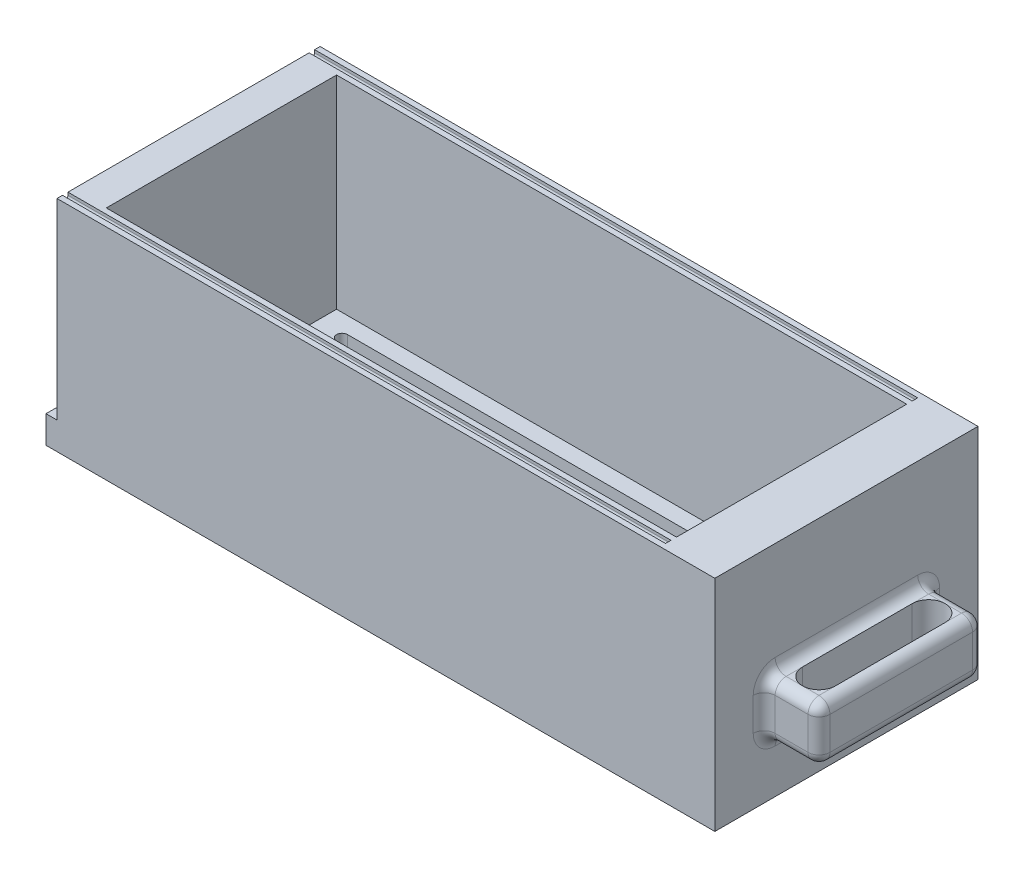
SolidWorks part; units mm, degrees
ref_plane "Front Plane" through (0, 0, 0) normal (0, 0, 1) x (1, 0, 0)
ref_plane "Top Plane" through (0, 0, 0) normal (0, 1, 0) x (1, 0, 0)
ref_plane "Right Plane" through (0, 0, 0) normal (1, 0, 0) x (0, 0, -1)
sketch "Sketch1" plane through (0, 0, 0) normal (0, 1, 0) x (1, 0, 0)
  line L1 (0, 0) -> (120, 0)
  line L2 (0, 0) -> (0, 48)
  line L3 (0, 48) -> (120, 48)
  line L4 (120, 0) -> (120, 48)
  dimension "D1" = 120
  dimension "D2" = 48
extrude "Boss-Extrude1" add sketch "Sketch1" along normal blind 40
sketch "Sketch2" plane through (0, 40, 0) normal (0, 1, 0) x (1, 0, 0)
  line L1 (6, 48) -> (74, 48)
  line L2 (6, 48) -> (6, 45)
  line L3 (6, 45) -> (74, 45)
  line L4 (74, 48) -> (74, 45)
  line L5 (120, 0) -> (120, 48) construction
  line L6 (0, 48) -> (120, 48) construction
  dimension "D1" = 3
  dimension "D2" = 46
  dimension "D3" = 68
extrude "Boss-Extrude2" [suppressed] add sketch "Sketch2" along normal blind 15
sketch "Sketch3" plane through (0, 40, 0) normal (0, 1, 0) x (1, 0, 0)
  line L1 (110, 45) -> (6, 45)
  line L2 (110, 45) -> (110, 3)
  line L3 (110, 3) -> (6, 3)
  line L4 (6, 45) -> (6, 3)
  line L5 (120, 0) -> (120, 48) construction
  line L6 (0, 0) -> (120, 0) construction
  line L7 (0, 48) -> (120, 48) construction
  dimension "D1" = 104
  dimension "D2" = 10
  dimension "D3" = 3
  dimension "D4" = 3
extrude "Cut-Extrude1" cut sketch "Sketch3" against normal blind 37
sketch "Sketch5" plane through (0, 3, 0) normal (0, 1, 0) x (1, 0, 0)
  line L0 (11, 41) -> (105, 41) construction
  line L1 (11, 42) -> (105, 42)
  line L2 (11, 40) -> (105, 40)
  line L3 (6, 45) -> (6, 3) construction
  line L4 (110, 3) -> (110, 45) construction
  line L5 (110, 45) -> (6, 45) construction
  line L8 (11, 35.1) -> (105, 35.1)
  line L11 (11, 37.1) -> (105, 37.1)
  line L14 (11, 36.1) -> (105, 36.1) construction
  line L17 (11, 30.2) -> (105, 30.2)
  line L20 (11, 32.2) -> (105, 32.2)
  line L23 (11, 31.2) -> (105, 31.2) construction
  line L26 (11, 25.3) -> (105, 25.3)
  line L28 (11, 27.3) -> (105, 27.3)
  line L29 (11, 26.3) -> (105, 26.3) construction
  line L30 (11, 20.4) -> (105, 20.4)
  line L31 (11, 22.4) -> (105, 22.4)
  line L32 (11, 21.4) -> (105, 21.4) construction
  line L33 (11, 15.5) -> (105, 15.5)
  line L34 (11, 17.5) -> (105, 17.5)
  line L35 (11, 16.5) -> (105, 16.5) construction
  line L36 (11, 10.6) -> (105, 10.6)
  line L37 (11, 12.6) -> (105, 12.6)
  line L38 (11, 11.6) -> (105, 11.6) construction
  line L39 (11, 5.7) -> (105, 5.7)
  line L40 (11, 7.7) -> (105, 7.7)
  line L41 (11, 6.7) -> (105, 6.7) construction
  arc A0 (11, 42) -> (11, 40) centre (11, 41) ccw
  arc A1 (105, 40) -> (105, 42) centre (105, 41) ccw
  arc A16 (11, 37.1) -> (11, 35.1) centre (11, 36.1) ccw
  arc A17 (105, 35.1) -> (105, 37.1) centre (105, 36.1) ccw
  arc A18 (11, 32.2) -> (11, 30.2) centre (11, 31.2) ccw
  arc A19 (105, 30.2) -> (105, 32.2) centre (105, 31.2) ccw
  arc A20 (11, 27.3) -> (11, 25.3) centre (11, 26.3) ccw
  arc A21 (105, 25.3) -> (105, 27.3) centre (105, 26.3) ccw
  arc A22 (11, 22.4) -> (11, 20.4) centre (11, 21.4) ccw
  arc A23 (105, 20.4) -> (105, 22.4) centre (105, 21.4) ccw
  arc A24 (11, 17.5) -> (11, 15.5) centre (11, 16.5) ccw
  arc A25 (105, 15.5) -> (105, 17.5) centre (105, 16.5) ccw
  arc A26 (11, 12.6) -> (11, 10.6) centre (11, 11.6) ccw
  arc A27 (105, 10.6) -> (105, 12.6) centre (105, 11.6) ccw
  arc A28 (11, 7.7) -> (11, 5.7) centre (11, 6.7) ccw
  arc A29 (105, 5.7) -> (105, 7.7) centre (105, 6.7) ccw
  point P2 (58, 41)
  point P17 (58, 36.1)
  point P24 (58, 31.2)
  point P31 (58, 26.3)
  point P38 (58, 21.4)
  point P45 (58, 16.5)
  point P52 (58, 11.6)
  point P59 (58, 6.7)
  dimension "D1" = 1
  dimension "D2" = 5
  dimension "D3" = 5
  dimension "D4" = 3
  dimension "D5" = 8
extrude "Cut-Extrude2" cut sketch "Sketch5" against normal blind 37
sketch "Sketch7" plane through (0, 0, 0) normal (-1, 0, 0) x (0, 0, 1)
  line L0 (-1.5, 39.5) -> (-1.5, 40.5) construction
  line L2 (-2, 39.5) -> (-2, 40.5)
  line L3 (-1, 39.5) -> (-1, 40.5)
  line L6 (-48, 40) -> (0, 40) construction
  line L7 (0, 40) -> (0, 0) construction
  arc A0 (-2, 39.5) -> (-1, 39.5) centre (-1.5, 39.5) ccw
  arc A1 (-1, 40.5) -> (-2, 40.5) centre (-1.5, 40.5) ccw
  point P4 (-1.5, 40)
  dimension "D2" = 0.5
  dimension "D1" = 1.5
  dimension "D3" = 1
extrude "Cut-Extrude4" cut sketch "Sketch7" against normal blind 110
ref_plane "Plane1" through (0, 0, -24) normal (0, 0, -1) x (-1, 0, 0)
mirror "Mirror1" about plane through (0, 0, -24) normal (0, 0, -1) of "Cut-Extrude4"
sketch "Sketch10" plane through (0, 0, 0) normal (-1, 0, 0) x (0, 0, 1)
  line L0 (0, 40) -> (0, 0) construction
  line L1 (-48, 0) -> (0, 0)
  line L2 (-48, 0) -> (-48, 5)
  line L3 (-48, 5) -> (0, 5)
  line L4 (0, 0) -> (0, 5)
  dimension "D1" = 5
extrude "Boss-Extrude3" add sketch "Sketch10" along normal blind 2
sketch "Sketch11" plane through (120, 0, 0) normal (1, 0, 0) x (0, 0, -1)
  line L0 (24, 20) -> (24, 10) construction
  line L1 (9, 20) -> (39, 20)
  line L2 (9, 20) -> (9, 10)
  line L3 (9, 10) -> (39, 10)
  line L4 (39, 20) -> (39, 10)
  line L5 (0, 40) -> (0, 0) construction
  dimension "D1" = 10
  dimension "D2" = 30
  dimension "D3" = 24
  dimension "D4" = 10
extrude "Boss-Extrude4" add sketch "Sketch11" along normal blind 10
sketch "Sketch12" plane through (0, 20, 0) normal (0, 1, 0) x (1, 0, 0)
  line L0 (125, 34) -> (125, 14) construction
  line L1 (128, 34) -> (128, 14)
  line L2 (122, 34) -> (122, 14)
  line L3 (130, 9) -> (120, 9) construction
  line L4 (130, 39) -> (120, 39) construction
  line L5 (130, 39) -> (130, 9) construction
  arc A0 (128, 34) -> (122, 34) centre (125, 34) ccw
  arc A1 (122, 14) -> (128, 14) centre (125, 14) ccw
  point P2 (125, 24)
  dimension "D1" = 5
  dimension "D2" = 5
  dimension "D4" = 3
  dimension "D3" = 5
extrude "Cut-Extrude6" cut sketch "Sketch12" against normal blind 8
fillet "Fillet1" radius 2 16 edges at (128, 12, -24) (125, 12, -11) (122, 12, -24) (125, 12, -37) (125, 10, -39) (125, 10, -9) (130, 10, -24) (130, 15, -9) (130, 15, -39) (120, 15, -39) (120, 10, -24) (120, 15, -9) (120, 20, -24) (125, 20, -9) (125, 20, -39) (130, 20, -24)
sketch "Sketch8" plane through (-2, 0, 0) normal (-1, 0, 0) x (0, 0, 1)
  line L0 (-48.5, 1.5) -> (-47.5, 1.5) construction
  line L1 (-48.5, 2) -> (-47.5, 2)
  line L2 (-48.5, 1) -> (-47.5, 1)
  line L3 (-48, 40) -> (-48, 5) construction
  line L4 (-48, 0) -> (0, 0) construction
  arc A0 (-48.5, 2) -> (-48.5, 1) centre (-48.5, 1.5) ccw
  arc A1 (-47.5, 1) -> (-47.5, 2) centre (-47.5, 1.5) ccw
  point P2 (-48, 1.5)
  dimension "D2" = 0.5
  dimension "D1" = 1
  dimension "D3" = 1.5
extrude "Cut-Extrude5" cut sketch "Sketch8" against normal blind 110
sketch "Sketch6" [suppressed] plane through (74, 0, 0) normal (1, 0, 0) x (0, 0, -1)
  line L1 (48, 40) -> (47, 40)
  line L2 (48, 40) -> (48, 45.2)
  line L3 (48, 45.2) -> (47, 45.2)
  line L4 (47, 40) -> (47, 45.2)
  dimension "D1" = 5.2
  dimension "D2" = 1
